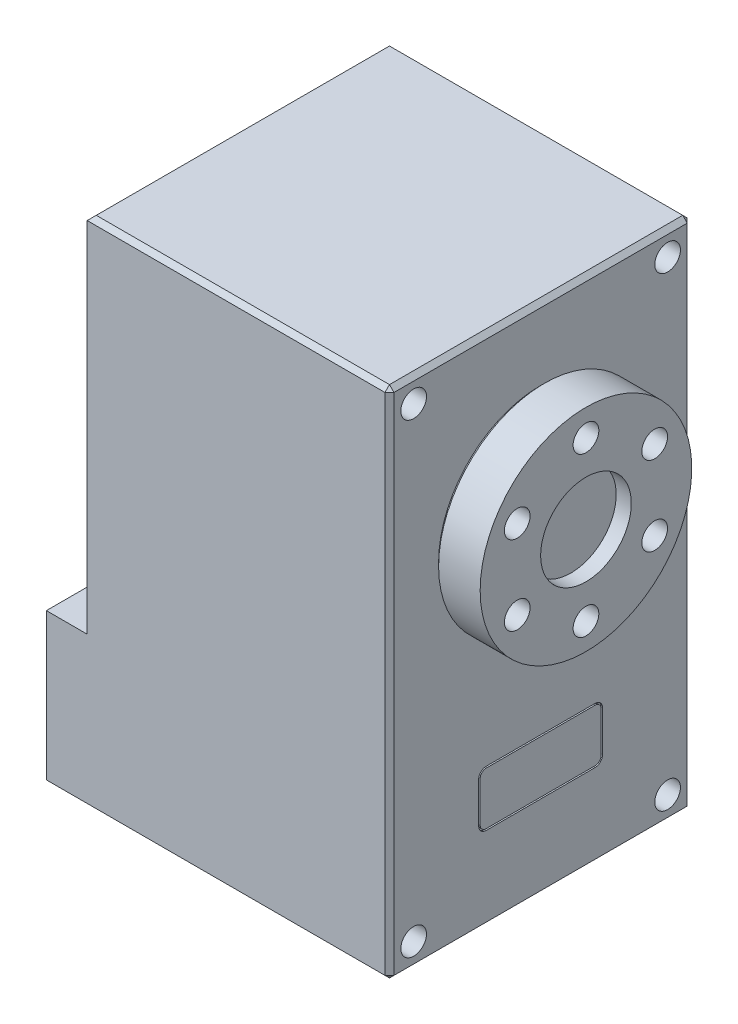
SolidWorks part; units mm, degrees
ref_plane "前视基准面" through (0, 0, 0) normal (0, 0, 1) x (1, 0, 0)
ref_plane "上视基准面" through (0, 0, 0) normal (0, 1, 0) x (1, 0, 0)
ref_plane "右视基准面" through (0, 0, 0) normal (1, 0, 0) x (0, 0, -1)
other "Configuration Table"
sketch "草图1" plane through (0, 0, 0) normal (0, 1, 0) x (1, 0, 0)
  line L1 (-10, -10) -> (10, -10)
  line L2 (-10, -10) -> (-10, 10)
  line L3 (-10, 10) -> (10, 10)
  line L4 (10, -10) -> (10, 10)
  line L5 (-10, -10) -> (10, 10) construction
  line L6 (-10, 10) -> (10, -10) construction
  point P0 (0, 0)
  dimension "D1" = 20
  dimension "D2" = 20
extrude "凸台-拉伸1" add sketch "草图1" along normal blind 34
sketch "草图2" plane through (-10, 0, 0) normal (-1, 0, 0) x (0, 0, 1)
  line L0 (0, 34) -> (0, 0) construction
  line L1 (-10, 34) -> (10, 34) construction
  circle A0 centre (0, 22.5) radius 6.75
  dimension "D2" = 13.5
  dimension "D1" = 11.5
extrude "凸台-拉伸3" add sketch "草图2" along normal blind 0.25
sketch "草图3" plane through (-10.25, 0, 0) normal (-1, 0, 0) x (0, 0, 1)
  circle A0 centre (0, 22.5) radius 7
  dimension "D1" = 14
extrude "凸台-拉伸4" add sketch "草图3" along normal blind 2.75
chamfer "倒角2" distance 0.25 angle 45 1 edges at (-10.25, 22.5, 6.75)
sketch "草图4" plane through (-13, 0, 0) normal (-1, 0, 0) x (0, 0, 1)
  circle A0 centre (0, 22.5) radius 5.25 construction
  circle A1 centre (0, 27.75) radius 0.85
  circle A2 centre (4.5466, 25.125) radius 0.85
  circle A3 centre (4.5466, 19.875) radius 0.85
  circle A4 centre (0, 17.25) radius 0.85
  circle A5 centre (-4.5466, 19.875) radius 0.85
  circle A6 centre (-4.5466, 25.125) radius 0.85
  point P17 (0, 22.5)
  dimension "D1" = 10.5
  dimension "D2" = 1.7
  dimension "D3" = 6
extrude "切除-拉伸1" cut sketch "草图4" against normal blind 3
mirror "镜向3" about plane through (0, 0, 0) normal (1, 0, 0) of "凸台-拉伸3", "凸台-拉伸4", "倒角2", "切除-拉伸1"
sketch "草图17" plane through (0, 0, 10) normal (0, 0, 1) x (1, 0, 0)
  line L1 (-10, 0) -> (-13, 0)
  line L2 (-10, 0) -> (-10, 10)
  line L3 (-10, 10) -> (-13, 10)
  line L4 (-13, 0) -> (-13, 10)
  dimension "D1" = 3
  dimension "D2" = 10
extrude "凸台-拉伸5" add sketch "草图17" against normal blind 20
sketch "草图18" plane through (-10, 0, 0) normal (-1, 0, 0) x (0, 0, 1)
  line L0 (0, 10) -> (0, 14.2893) construction
  line L1 (10, 10) -> (7.5, 10) construction
  line L2 (10, 10) -> (10, 17) construction
  line L3 (10, 17) -> (7.5, 17) construction
  line L4 (7.5, 10) -> (7.5, 17) construction
  line L5 (7.5, 10) -> (5, 10)
  line L6 (7.5, 10) -> (7.5, 17)
  line L7 (7.5, 17) -> (5, 17)
  line L8 (5, 10) -> (5, 12.35)
  line L9 (7.5, 13.5) -> (1.7357, 13.5) construction
  line L14 (5, 14.65) -> (4.2579, 14.65)
  line L15 (4.2579, 14.65) -> (4.2579, 12.35)
  line L16 (4.2579, 12.35) -> (5, 12.35)
  line L17 (5, 14.65) -> (5, 17)
  line L18 (7.8, 17) -> (7.8, 10)
  line L19 (7.8, 10) -> (9.75, 10)
  line L20 (9.75, 10) -> (9.75, 17)
  line L21 (9.75, 17) -> (7.8, 17)
  dimension "D1" = 7
  dimension "D2" = 2.5
  dimension "D3" = 2.5
  dimension "D4" = 7
  dimension "D5" = 2.3
  dimension "D6" = 0.5
  dimension "D7" = 0.3
extrude "切除-拉伸3" cut sketch "草图18" against normal blind 5
sketch "草图19" plane through (0, 0, 7.5) normal (0, 0, -1) x (-1, 0, 0)
  line L0 (10, 13.5) -> (3.5202, 13.5) construction
  line L1 (10, 10) -> (10, 17) construction
  line L3 (9.8, 15.25) -> (5, 15.25)
  line L4 (9.8, 13.65) -> (5, 13.65)
  line L5 (9.8, 13.65) -> (9.8, 13.35)
  line L6 (9.8, 13.35) -> (5, 13.35)
  line L7 (5, 13.65) -> (5, 13.35)
  line L8 (9.8, 15.25) -> (9.8, 14.95)
  line L9 (9.8, 14.95) -> (5, 14.95)
  line L10 (5, 15.25) -> (5, 14.95)
  line L11 (9.8, 11.75) -> (9.8, 12.05)
  line L12 (9.8, 12.05) -> (5, 12.05)
  line L13 (5, 11.75) -> (5, 12.05)
  line L14 (9.8, 11.75) -> (5, 11.75)
  line L15 (10, 34) -> (10, 10) construction
  dimension "D1" = 4.8
  dimension "D2" = 0.3
  dimension "D3" = 1.75
  dimension "D4" = 0.2
  dimension "D5" = 0.2
  dimension "D6" = 0.3
  dimension "D7" = 4.8
extrude "凸台-拉伸6" add sketch "草图19" along normal blind 0.3
sketch "草图21" plane through (-5, 0, 0) normal (-1, 0, 0) x (0, 0, 1)
  line L0 (9.75, 13.5) -> (11.3477, 13.5) construction
  line L2 (9.75, 14.2503) -> (9.6262, 14.2503)
  line L3 (9.75, 10) -> (9.75, 17) construction
  line L4 (9.6262, 14.2503) -> (9.6262, 14.5555)
  line L5 (9.6262, 14.5555) -> (9.75, 14.5555)
  line L6 (9.75, 14.5555) -> (9.75, 14.2503)
  line L7 (9.6262, 12.4445) -> (9.75, 12.4445)
  line L8 (9.6262, 12.7497) -> (9.6262, 12.4445)
  line L9 (9.75, 12.7497) -> (9.6262, 12.7497)
  line L10 (9.75, 12.4445) -> (9.75, 12.7497)
extrude "凸台-拉伸7" add sketch "草图21" along normal blind 4.8
chamfer "倒角3" distance 0.2 angle 45 11 edges at (-10, 17, 8.775) (-10, 13.5, 9.75) (-10, 13.5, 7.5) (-10, 17, 6.25) (-10, 11.175, 5) (-7.5, 12.35, 5) (-10, 12.35, 4.6289) (-10, 15.825, 5) (-7.5, 14.65, 5) (-10, 14.65, 4.6289) (-10, 13.5, 4.2579)
mirror "镜向5" about plane through (0, 0, 0) normal (0, 0, 1) of "倒角3", "凸台-拉伸7", "凸台-拉伸6", "切除-拉伸3"
sketch "草图22" plane through (0, 0, 0) normal (0, 0, 1) x (1, 0, 0)
  line L0 (-13, 10) -> (-10, 15.4143)
  line L2 (-10, 10) -> (-13, 10) construction
  line L3 (-10, 34) -> (-10, 10) construction
  point P2 (-13.0031, 10)
  point P3 (-12.9932, 10)
rib "筋16" sketch "草图22" sketch "草图22" thickness 8 extrusion direction parallel to sketch draft on no parameters "D1"=8
sketch "草图23" plane through (-13, 0, 0) normal (-1, 0, 0) x (0, 0, 1)
  line L0 (4, 15.4143) -> (4, 10) construction
  line L1 (-4, 15.4143) -> (4, 15.4143)
  arc A0 (-4, 15.4143) -> (4, 15.4143) centre (0, 19.4171) ccw
extrude "切除-拉伸4" cut sketch "草图23" against normal blind 3
sketch "草图24" plane through (-14.1857, 7.8601, 0) normal (-0.8747, 0.4847, 0) x (0, 0, 1)
  line L0 (0, 2.4465) -> (0, 8.6364) construction
  line L1 (-1.8527, 5.0706) -> (1.8527, 5.0706)
  line L2 (-1.8527, 5.0706) -> (-1.8527, 6.4792)
  line L3 (-1.8527, 6.4792) -> (1.8527, 6.4792)
  line L4 (1.8527, 5.0706) -> (1.8527, 6.4792)
  line L5 (-1.8527, 5.0706) -> (1.8527, 6.4792) construction
  line L6 (-1.8527, 6.4792) -> (1.8527, 5.0706) construction
  point P0 (0, 5.7749)
  point P7 (0, 5.5723)
  point P8 (0, 5.7749)
extrude "切除-拉伸-薄壁1" cut sketch "草图24" against normal blind 0.1 thin
sketch "草图25" plane through (10, 0, 0) normal (1, 0, 0) x (0, 0, -1)
  line L0 (0, 0) -> (0, 13.0314) construction
  line L2 (-3.5996, 5.6575) -> (3.5996, 5.6575)
  line L3 (-3.9996, 6.0575) -> (-3.9996, 8.73)
  line L4 (-3.5996, 9.13) -> (3.5996, 9.13)
  line L5 (3.9996, 6.0575) -> (3.9996, 8.73)
  line L6 (-3.9996, 5.6575) -> (3.9996, 9.13) construction
  line L7 (-3.9996, 9.13) -> (3.9996, 5.6575) construction
  arc A0 (-3.5996, 5.6575) -> (-3.9996, 6.0575) centre (-3.5996, 6.0575) cw
  arc A1 (3.5996, 5.6575) -> (3.9996, 6.0575) centre (3.5996, 6.0575) ccw
  arc A2 (3.5996, 9.13) -> (3.9996, 8.73) centre (3.5996, 8.73) cw
  arc A3 (-3.9996, 8.73) -> (-3.5996, 9.13) centre (-3.5996, 8.73) cw
  point P3 (0, 7.3938)
  point P8 (0, 7.3938)
  dimension "D1" = 0.4
extrude "切除-拉伸-薄壁2" cut sketch "草图25" against normal blind 0.1 thin
sketch "草图26" plane through (-13, 0, 0) normal (-1, 0, 0) x (0, 0, 1)
  circle A0 centre (0, 22.5) radius 3
  dimension "D1" = 6
extrude "切除-拉伸5" cut sketch "草图26" against normal blind 1
mirror "镜向6" about plane through (0, 0, 0) normal (1, 0, 0) of "切除-拉伸5"
sketch "草图27" plane through (-13, 0, 0) normal (-1, 0, 0) x (0, 0, 1)
  line L0 (0, 0) -> (0, 6.6188) construction
  circle A0 centre (8.5194, 1.3852) radius 0.85
  circle A1 centre (-8.5194, 1.3852) radius 0.85
  point P5 (8.507, 1.4578)
  point P6 (8.5194, 1.3852)
  dimension "D1" = 1.7
extrude "切除-拉伸6" cut sketch "草图27" against normal blind 3
sketch "草图28" plane through (-10, 0, 0) normal (-1, 0, 0) x (0, 0, 1)
  line L0 (8.5194, 1.3852) -> (8.5194, 36.2658) construction
  line L1 (0, 0) -> (0, 36.2658) construction
  line L2 (-10, 0) -> (10, 0) construction
  circle A0 centre (8.5194, 32.5825) radius 0.85
  circle A1 centre (-8.5194, 32.5825) radius 0.85
  point P9 (8.5194, 32.5825)
  dimension "D1" = 1.7
extrude "切除-拉伸7" cut sketch "草图28" against normal blind 3
sketch "草图30" plane through (10, 0, 0) normal (1, 0, 0) x (0, 0, -1)
  line L16 (-8.4, 1.6) -> (8.4, 1.6)
  line L17 (8.4, 1.6) -> (8.4, 32.4)
  line L18 (8.4, 32.4) -> (-8.4, 32.4)
  line L19 (-8.4, 32.4) -> (-8.4, 1.6)
  line L20 (-8.4, 1.6) -> (8.4, 1.6) construction
  line L21 (8.4, 1.6) -> (8.4, 32.4) construction
  line L22 (8.4, 32.4) -> (-8.4, 32.4) construction
  line L23 (-8.4, 32.4) -> (-8.4, 1.6) construction
  circle A0 centre (-8.4, 32.4) radius 0.85
  circle A1 centre (8.4, 32.4) radius 0.85
  circle A2 centre (8.4, 1.6) radius 0.85
  circle A3 centre (-8.4, 1.6) radius 0.85
  dimension "D2" = 1.7
  dimension "D3" = 1.7
  dimension "D4" = 1.7
  dimension "D5" = 1.7
  dimension "D1" = 1.6
extrude "切除-拉伸8" cut sketch "草图30" against normal blind 3
chamfer "倒角4" distance 0.3 angle 45 12 edges at (10, 17, -10) (0, 34, -10) (10, 34, 0) (-10, 34, 0) (0, 34, 10) (-13, 10, -7) (10, 17, 10) (10, 0, 0) (-1.5, 0, 10) (-13, 5, -10) (-1.5, 0, -10) (-13, 0, 0)
